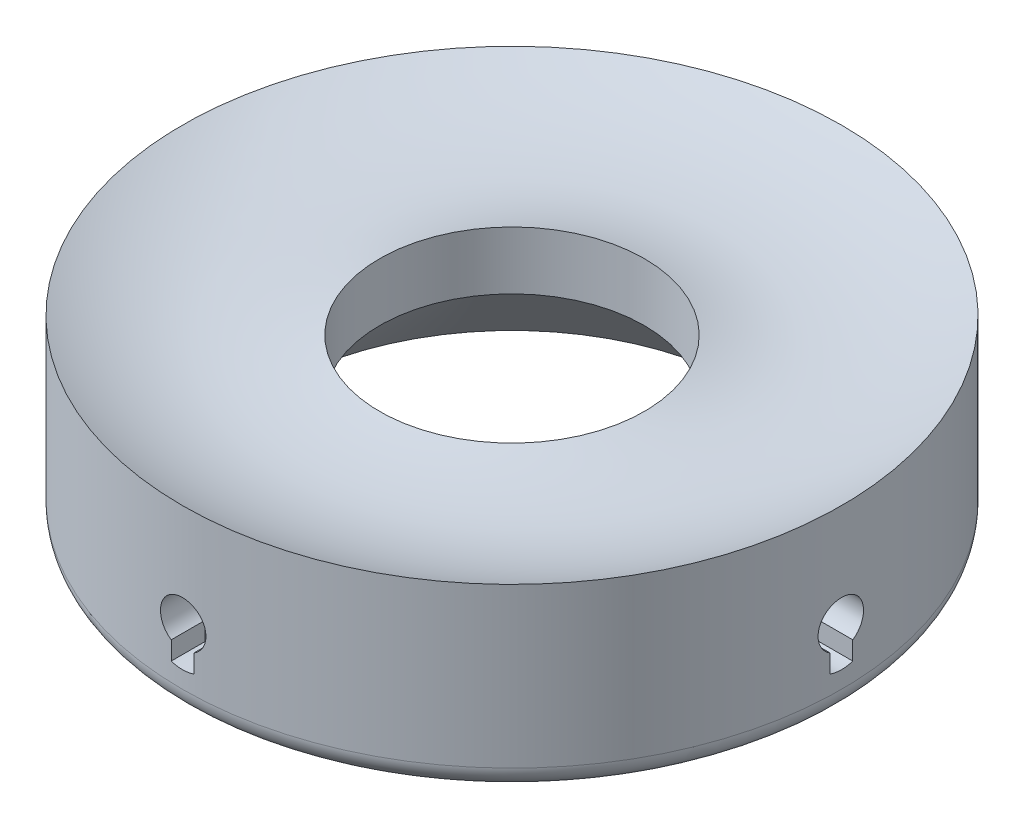
SolidWorks part; units mm, degrees
material "Polyester Resin"
ref_plane "Front Plane" through (0, 0, 0) normal (0, 0, 1) x (1, 0, 0)
ref_plane "Top Plane" through (0, 0, 0) normal (0, 1, 0) x (1, 0, 0)
ref_plane "Right Plane" through (0, 0, 0) normal (1, 0, 0) x (0, 0, -1)
sketch "Sketch1" plane through (0, 0, 0) normal (0, 1, 0) x (1, 0, 0)
  circle A0 centre (0, 0) radius 36.83
extrude "Boss-Extrude1" add sketch "Sketch1" along normal blind 20.32
fillet "Fillet1" radius 2.54 1 edges at (0, 0, 36.83)
sketch "Sketch2" plane through (0, 0, 0) normal (0, 1, 0) x (1, 0, 0)
  circle A0 centre (0, 0) radius 26.67
  dimension "D1" = 53.34
ref_plane "Plane1" through (0, 11.938, 0) normal (0, 1, 0) x (1, 0, 0)
sketch "Sketch3" plane through (0, 11.938, 0) normal (0, 1, 0) x (1, 0, 0)
  circle A0 centre (0, 0) radius 14.7955
  dimension "D1" = 29.591
loft "Cut-Loft1" cut profiles "Sketch2", "Sketch3" connector at (-21.548, 0, -15.7154) connector at (-12.1049, 11.938, -8.5075)
sketch "Sketch4" plane through (0, 11.938, 0) normal (0, -1, 0) x (1, 0, 0)
  circle A0 centre (0, 0) radius 14.7955 construction
  circle A1 centre (0, 0) radius 14.7955
extrude "Cut-Extrude1" cut sketch "Sketch4" against normal blind 76.2
ref_plane "Plane2" through (0, 13.97, 0) normal (0, 1, 0) x (1, 0, 0)
ref_plane "Plane3" through (0, 0, 36.83) normal (0, 0, 1) x (1, 0, 0)
sketch "Sketch8" plane through (0, 0, 36.83) normal (0, 0, 1) x (1, 0, 0)
  line L1 (0, 0) -> (0, 8.89) construction
  circle A0 centre (0, 8.89) radius 2.54
  dimension "D1" = 5.08
extrude "Cut-Extrude2" cut sketch "Sketch8" against normal blind 6.35
pattern_circular "CirPattern1" count 4 over 360 about axis through (0, 0, 0) along (0, -1, 0) of "Cut-Extrude2"
sketch "Sketch9" plane through (0, 0, 36.83) normal (0, 0, 1) x (1, 0, 0)
  line L0 (0, 6.35) -> (0, 4.445) construction
  line L1 (-1.27, 4.445) -> (1.27, 4.445)
  line L2 (1.27, 4.445) -> (1.27, 6.6903)
  line L3 (-1.27, 4.445) -> (-1.27, 6.6903)
  circle A0 centre (0, 8.89) radius 2.54 construction
  circle A1 centre (0, 8.89) radius 2.54 construction
  arc A4 (-1.27, 6.6903) -> (1.27, 6.6903) centre (0, 8.89) ccw
  point P20 (0, 8.89)
  dimension "D1" = 2.54
  dimension "D2" = 1.905
extrude "Cut-Extrude3" cut sketch "Sketch9" against normal blind 6.35
sketch "Sketch10" plane through (0, 0, 30.48) normal (0, 0, 1) x (1, 0, 0)
  circle A0 centre (0, 8.89) radius 4.445
  dimension "D1" = 8.89
extrude "Cut-Extrude4" cut sketch "Sketch10" along normal blind 2.54
sketch "Sketch11" plane through (0, 0, 30.48) normal (0, 0, 1) x (1, 0, 0)
  line L0 (-2.54, 8.89) -> (-4.445, 8.89)
  line L2 (1.27, 4.6303) -> (1.27, 6.6903)
  arc A0 (1.27, 4.6303) -> (-4.445, 8.89) centre (0, 8.89) ccw
  arc A2 (1.27, 6.6903) -> (-1.27, 6.6903) centre (0, 8.89) ccw construction
  arc A3 (1.27, 6.6903) -> (-2.54, 8.89) centre (0, 8.89) ccw
extrude "Boss-Extrude2" add sketch "Sketch11" along normal blind 2.54
sketch "Sketch12" plane through (0, 0, 30.48) normal (0, 0, 1) x (1, 0, 0)
  line L0 (1.27, 4.445) -> (-1.27, 4.445) construction
  line L1 (1.27, 4.445) -> (-1.27, 4.445)
  line L2 (-1.27, 4.445) -> (-1.27, 6.6903) construction
  line L3 (1.27, 4.445) -> (1.27, 6.6903) construction
  line L4 (-1.27, 4.445) -> (-1.27, 4.6303)
  line L5 (1.27, 4.445) -> (1.27, 4.6303)
  arc A0 (-1.27, 4.6303) -> (1.27, 4.6303) centre (0, 8.89) ccw
  line M1 (1.27, 4.445) -> (1.27, 6.6903)
  line M5 (-1.27, 4.6303) -> (-1.27, 4.445)
  line M6 (-1.27, 4.445) -> (1.27, 4.445)
extrude "Boss-Extrude3" add sketch "Sketch12" along normal blind 6.35 contours A0 M5 M6 | A0 L1 M1 region at (-0.9538, 4.5004, 30.48) region at (0.9538, 4.5004, 30.48)
sketch "Sketch13" plane through (0, 0, 0) normal (0, -1, 0) x (1, 0, 0)
  circle A0 centre (0, 0) radius 36.83
  circle A1 centre (0, 0) radius 39.9751
extrude "Cut-Extrude5" cut sketch "Sketch13" against normal blind 21.59
pattern_circular "CirPattern2" count 4 over 360 about axis through (0, 0, 0) along (0, -1, 0) of "Cut-Extrude3", "Cut-Extrude4", "Boss-Extrude2", "Cut-Extrude5", "Boss-Extrude3"
sketch "Sketch17" plane through (0, 0, 0) normal (1, 0, 0) x (0, 0, -1)
  line L0 (0, 0) -> (0, 18.415) construction
  line L3 (36.83, 20.32) -> (14.7955, 20.32)
  line L4 (14.7955, 20.32) -> (14.7955, 18.415)
  arc A0 (36.83, 20.32) -> (14.7955, 18.415) centre (23.2492, 49.0189) cw
  dimension "D2" = 31.75
  dimension "D1" = 18.415
  dimension "D3" = 14.7955
revolve "Cut-Revolve1" cut sketch "Sketch17" angle 360 about L0
